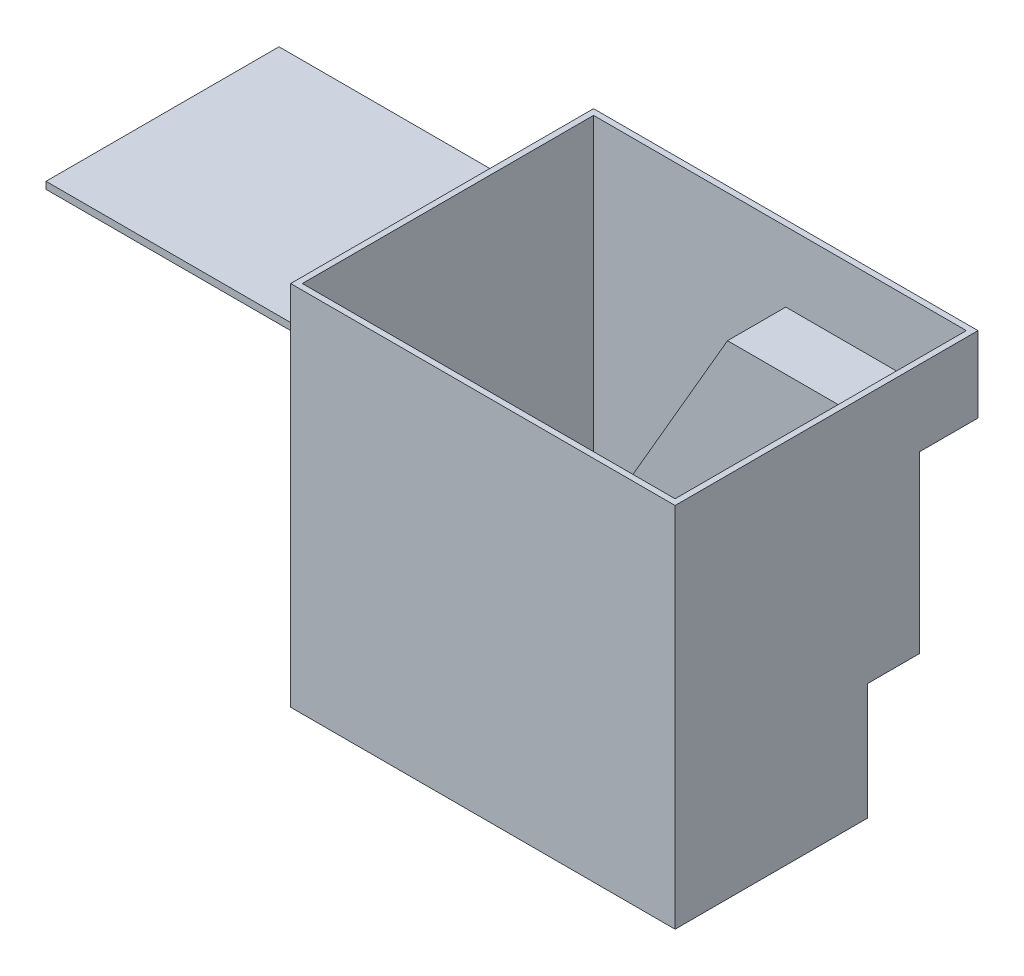
SolidWorks part; units mm, degrees
material "松木"
ref_plane "前视基准面" through (0, 0, 0) normal (0, 0, 1) x (1, 0, 0)
ref_plane "上视基准面" through (0, 0, 0) normal (0, 1, 0) x (1, 0, 0)
ref_plane "右视基准面" through (0, 0, 0) normal (1, 0, 0) x (0, 0, -1)
other "Configuration Table"
sketch "草图1" plane through (0, 0, 0) normal (0, 1, 0) x (1, 0, 0)
  line L0 (0, 300) -> (0, 510)
  line L1 (0, 0) -> (800, 0)
  line L2 (0, 0) -> (0, 300)
  line L3 (160, 320) -> (800, 320)
  line L4 (800, 0) -> (800, 320)
  line L5 (0, 510) -> (160, 510)
  line L6 (160, 510) -> (160, 320)
  dimension "D1" = 800
  dimension "D2" = 190
  dimension "D3" = 320
  dimension "D4" = 160
extrude "凸台-拉伸1" add sketch "草图1" along normal blind 10
sketch "草图2" plane through (0, 10, 0) normal (0, 1, 0) x (1, 0, 0)
  line L0 (160, 510) -> (0, 510) construction
  line L1 (0, 0) -> (10, 0)
  line L2 (0, 0) -> (0, 510)
  line L3 (0, 510) -> (10, 510)
  line L4 (10, 0) -> (10, 510)
  dimension "D1" = 10
extrude "凸台-拉伸2" add sketch "草图2" along normal blind 500
sketch "草图3" plane through (0, 0, -510) normal (0, 0, -1) x (-1, 0, 0)
  line L0 (-10, 510) -> (-10, 10)
  line L1 (-10, 10) -> (-160, 10)
  line L2 (-160, 10) -> (-450.0087, 510)
  line L3 (-450.0087, 510) -> (-10, 510)
extrude "凸台-拉伸3" add sketch "草图3" against normal blind 10
sketch "草图4" plane through (0, 0, -510) normal (0, 0, -1) x (-1, 0, 0)
  line L0 (-276.0035, 210) -> (-160, 10)
  line L1 (-160, 10) -> (-160, 0)
  line L2 (-160, 10) -> (-160, 0) construction
  line L3 (-160, 0) -> (-169.7622, 0)
  line L4 (-800, 0) -> (-160, 0) construction
  line L5 (-169.7622, 0) -> (-169.7622, 10)
  line L6 (-800, 10) -> (-160, 10) construction
  line L7 (-169.7622, 10) -> (-285.7657, 210)
  line L9 (-285.7657, 210) -> (-276.0035, 210)
  dimension "D1" = 200
extrude "凸台-拉伸4" add sketch "草图4" against normal up to surface (190 mm away) up to face at (480, 5, -320)
sketch "草图5" plane through (0, 10, 0) normal (0, 1, 0) x (1, 0, 0)
  line L1 (800, 320) -> (160, 320)
  line L2 (800, 320) -> (800, 310)
  line L3 (800, 310) -> (160, 310)
  line L4 (160, 320) -> (160, 310)
  dimension "D1" = 10
extrude "凸台-拉伸5" add sketch "草图5" along normal blind 200
sketch "草图6" plane through (0, 0, -320) normal (0, 0, -1) x (-1, 0, 0)
  line L0 (-160, 210) -> (-276.0035, 210)
  line L1 (-276.0035, 210) -> (-160, 10)
  line L2 (-160, 10) -> (-160, 210)
extrude "切除-拉伸1" cut sketch "草图6" against normal blind 20
sketch "草图7" plane through (0, 210, 0) normal (0, 1, 0) x (1, 0, 0)
  line L6 (276.0035, 310) -> (800, 310)
  line L7 (276.0035, 310) -> (276.0035, 410)
  line L8 (276.0035, 410) -> (800, 410)
  line L9 (800, 310) -> (800, 410)
  dimension "D1" = 100
extrude "凸台-拉伸7" add sketch "草图7" against normal blind 10
sketch "草图8" plane through (0, 0, -510) normal (0, 0, -1) x (-1, 0, 0)
  line L0 (-276.0035, 210) -> (-450.0087, 510)
  line L1 (-276.0035, 210) -> (-285.7657, 210)
  line L2 (-285.7657, 210) -> (-459.7709, 510)
  line L3 (-459.7709, 510) -> (-450.0087, 510)
extrude "凸台-拉伸8" add sketch "草图8" against normal up to surface (100 mm away) up to face at (541.4328, 205, -410)
sketch "草图9" plane through (0, 0, -410) normal (0, 0, 1) x (1, 0, 0)
  line L0 (276.0035, 210) -> (450.0087, 510)
  line L1 (450.0087, 510) -> (800, 510)
  line L2 (800, 510) -> (800, 210)
  line L3 (800, 210) -> (276.0035, 210)
extrude "凸台-拉伸9" add sketch "草图9" along normal blind 10
sketch "草图10" plane through (800, 0, 0) normal (1, 0, 0) x (0, 0, -1)
  line L0 (0, 0) -> (320, 0)
  line L1 (320, 0) -> (320, 200)
  line L2 (320, 200) -> (410, 200)
  line L3 (410, 200) -> (410, 510)
  line L4 (410, 510) -> (0, 510)
  line L5 (0, 510) -> (0, 0)
extrude "凸台-拉伸10" add sketch "草图10" along normal blind 10
sketch "草图11" plane through (0, 0, 0) normal (0, 0, 1) x (1, 0, 0)
  line L1 (0, 510) -> (810, 510)
  line L2 (0, 510) -> (0, 0)
  line L3 (0, 0) -> (810, 0)
  line L4 (810, 510) -> (810, 0)
extrude "凸台-拉伸11" add sketch "草图11" along normal blind 10
sketch "草图12" plane through (0, 0, 0) normal (-1, 0, 0) x (0, 0, 1)
  line L1 (-510, 510) -> (10, 510)
  line L2 (-510, 510) -> (-510, 0)
  line L3 (-510, 0) -> (10, 0)
  line L4 (10, 510) -> (10, 0)
extrude "切除-拉伸2" cut sketch "草图12" against normal blind 120
sketch "草图13" plane through (810, 0, 0) normal (1, 0, 0) x (0, 0, -1)
  line L1 (-10, 510) -> (510, 510)
  line L2 (-10, 510) -> (-10, 0)
  line L3 (-10, 0) -> (510, 0)
  line L4 (510, 510) -> (510, 0)
extrude "切除-拉伸3" cut sketch "草图13" against normal blind 50
sketch "草图14" plane through (760, 0, 0) normal (1, 0, 0) x (0, 0, -1)
  line L1 (-10, 510) -> (320, 510)
  line L2 (-10, 510) -> (-10, 0)
  line L3 (-10, 0) -> (320, 0)
  line L4 (320, 200) -> (320, 0)
  line L5 (320, 510) -> (410, 510)
  line L7 (320, 200) -> (410, 200)
  line L8 (410, 510) -> (410, 200)
extrude "凸台-拉伸12" add sketch "草图14" along normal blind 10
sketch "草图15" plane through (120, 0, 0) normal (-1, 0, 0) x (0, 0, 1)
  line L1 (-510, 510) -> (10, 510)
  line L2 (-510, 510) -> (-510, 0)
  line L3 (-510, 0) -> (10, 0)
  line L4 (10, 510) -> (10, 0)
extrude "凸台-拉伸13" add sketch "草图15" along normal blind 10
sketch "草图17" plane through (0, 0, -410) normal (0, 0, -1) x (-1, 0, 0)
  line L0 (-770, 510) -> (-459.7709, 510)
  line L1 (-459.7709, 510) -> (-453.9707, 500)
  line L2 (-459.7709, 510) -> (-169.7622, 10) construction
  line L3 (-453.9707, 500) -> (-770, 500)
  line L4 (-770, 200) -> (-770, 510) construction
  line L5 (-770, 500) -> (-770, 510)
  dimension "D1" = 10
extrude "凸台-拉伸15" add sketch "草图17" along normal up to surface (100 mm away) up to face at (203.8591, 206, -510)
sketch "草图18" plane through (0, 510, 0) normal (0, 1, 0) x (1, 0, 0)
  line L1 (110, 510) -> (770, 510)
  line L2 (110, 510) -> (110, -10)
  line L3 (110, -10) -> (770, -10)
  line L4 (770, 510) -> (770, -10)
  line L5 (120, 500) -> (760, 500)
  line L6 (120, 500) -> (120, 0)
  line L7 (120, 0) -> (760, 0)
  line L8 (760, 500) -> (760, 0)
extrude "凸台-拉伸16" add sketch "草图18" along normal blind 120
sketch "草图19" plane through (110, 0, 0) normal (-1, 0, 0) x (0, 0, 1)
  line L0 (-510, 0) -> (10, 0) construction
  line L1 (-450, 512) -> (-50, 512)
  line L2 (-450, 512) -> (-450, 500)
  line L3 (-450, 500) -> (-50, 500)
  line L4 (-50, 512) -> (-50, 500)
  line L5 (-510, 630) -> (10, 630) construction
  point P6 (-250, 512)
  point P9 (-250, 630)
  dimension "D1" = 12
  dimension "D2" = 500
  dimension "D3" = 0
  dimension "D4" = 400
extrude "凸台-拉伸17" add sketch "草图19" along normal blind 480
